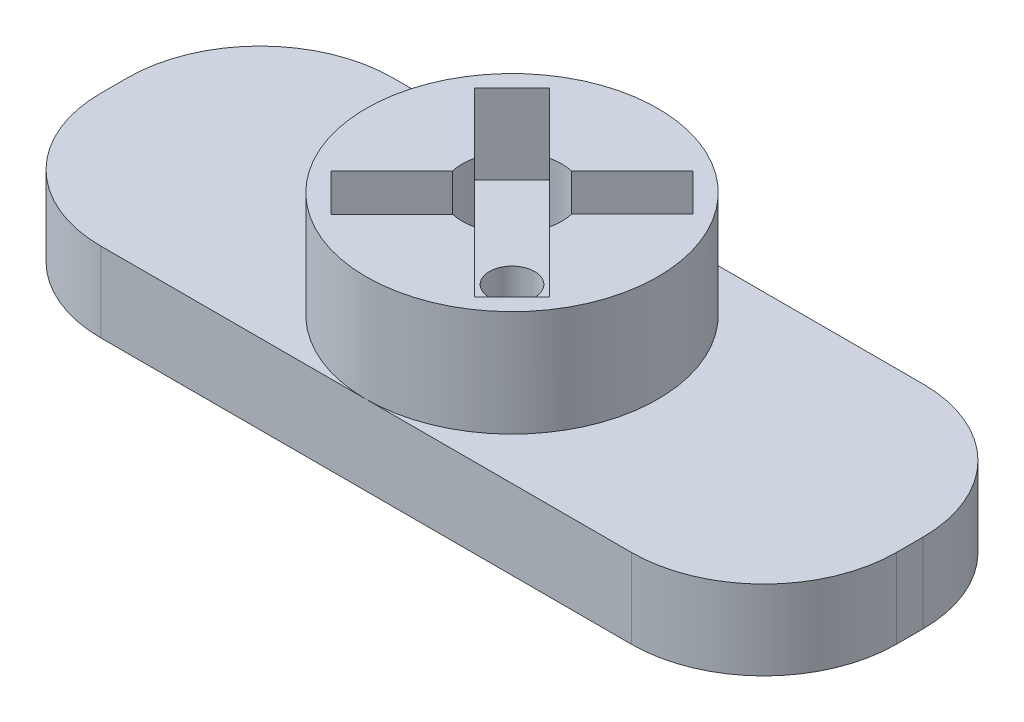
SolidWorks part; units mm, degrees
ref_plane "Płaszczyzna przednia" through (0, 0, 0) normal (0, 0, 1) x (1, 0, 0)
ref_plane "Płaszczyzna górna" through (0, 0, 0) normal (0, 1, 0) x (1, 0, 0)
ref_plane "Płaszczyzna prawa" through (0, 0, 0) normal (1, 0, 0) x (0, 0, -1)
sketch "Sketch1" plane through (0, 0, 0) normal (0, 1, 0) x (1, 0, 0)
  line L5 (-20.01, -11) -> (20.01, -11)
  line L6 (-30, -1.01) -> (-30, 1.01)
  line L7 (-20.01, 11) -> (20.01, 11)
  line L8 (30, -1.01) -> (30, 1.01)
  line L9 (-30, -11) -> (30, 11) construction
  line L10 (-30, 11) -> (30, -11) construction
  arc A0 (-20.01, -11) -> (-30, -1.01) centre (-20.01, -1.01) cw
  arc A1 (20.01, -11) -> (30, -1.01) centre (20.01, -1.01) ccw
  arc A2 (20.01, 11) -> (30, 1.01) centre (20.01, 1.01) cw
  arc A3 (-30, 1.01) -> (-20.01, 11) centre (-20.01, 1.01) cw
  point P0 (0, 0)
  point P1 (0, 0)
  dimension "D3" = 9.99
  dimension "D1" = 60
  dimension "D2" = 22
extrude "Boss-Extrude1" add sketch "Sketch1" along normal blind 6
sketch "Sketch2" plane through (0, 6, 0) normal (0, 1, 0) x (1, 0, 0)
  line L0 (0, 0) -> (-3, 0) construction
  line L1 (0, 0) -> (3, 0) construction
  circle A3 centre (0, 0) radius 11
extrude "Boss-Extrude2" add sketch "Sketch2" along normal blind 8
sketch "Sketch5" plane through (0, 14, 0) normal (0, 1, 0) x (1, 0, 0)
  line L0 (-6.8226, 6.8246) -> (-5.4081, 8.2386) construction
  line L39 (-5.4081, 8.2386) -> (-6.8226, 6.8246) construction
  line L40 (-6.8226, 6.8246) -> (-8.237, 5.4106) construction
  line L41 (6.8226, 6.8246) -> (5.4085, 8.239) construction
  line L42 (6.8226, 6.8246) -> (8.2366, 5.4102) construction
  line L43 (6.8226, -6.8246) -> (8.237, -5.4106) construction
  line L44 (6.8226, -6.8246) -> (5.4081, -8.2386) construction
  line L45 (-6.8226, -6.8246) -> (-8.2366, -5.4102) construction
  line L46 (-6.8226, -6.8246) -> (-5.4085, -8.239) construction
  line L47 (-8.237, 5.4106) -> (-3.6571, 0.8294)
  line L48 (5.4081, -8.2386) -> (8.237, -5.4106)
  line L49 (8.237, -5.4106) -> (3.6571, -0.8294)
  line L50 (-5.4081, 8.2386) -> (-8.237, 5.4106)
  line L51 (-5.4085, -8.239) -> (-0.8283, -3.6574)
  line L52 (8.2366, 5.4102) -> (5.4085, 8.239)
  line L53 (5.4085, 8.239) -> (0.8283, 3.6574)
  line L54 (-8.2366, -5.4102) -> (-5.4085, -8.239)
  line L55 (0.8283, -3.6574) -> (5.4081, -8.2386)
  line L56 (3.6571, 0.8294) -> (8.2366, 5.4102)
  line L58 (-0.8283, 3.6574) -> (-5.4081, 8.2386)
  line L60 (-3.6571, -0.8294) -> (-8.2366, -5.4102)
  arc A8 (-0.8283, -3.6574) -> (0.8283, -3.6574) centre (0, 0) ccw
  arc A10 (3.6571, -0.8294) -> (3.6571, 0.8294) centre (0, 0) ccw
  arc A11 (0.8283, 3.6574) -> (-0.8283, 3.6574) centre (0, 0) ccw
  arc A12 (-3.6571, 0.8294) -> (-3.6571, -0.8294) centre (0, 0) ccw
  dimension "D6" = 2
  dimension "D7" = 9.65
  dimension "D8" = 9.65
  dimension "D9" = 9.65
  dimension "D10" = 9.65
extrude "Cut-Extrude1" cut sketch "Sketch5" against normal blind 6
sketch "Sketch12" plane through (0, 0, 0) normal (0, -1, 0) x (1, 0, 0)
  circle A0 centre (0, 0) radius 6
extrude "Cut-Extrude2" cut sketch "Sketch12" against normal blind 4
sketch "Sketch18" plane through (0, 4, 0) normal (0, -1, 0) x (-1, 0, 0)
  point P0 (0, 0)
hole_wizard "CSK for M3 Countersunk Flat Head Screw3" positions "Sketch18" profile "Sketch17" countersink size "M3" standard "ISO" end condition through all
sketch "Sketch17" plane through (0, 4, 0) normal (1, 0, 0) x (0, 0, -1)
  line L0 (0, 0) -> (0, 10)
  line L1 (0, 10) -> (1.7, 10)
  line L2 (1.7, 10) -> (1.7, 1.45)
  line L3 (1.7, 1.45) -> (3.15, 0)
  line L5 (3.15, 0) -> (0, 0)
  line L6 (-1.7, 1.45) -> (-3.15, 0) construction
  line L11 (0, -6.35) -> (0, 107.95) construction
  dimension "Thru Hole Dia." = 3.4
  dimension "Thru Hole Depth" = 10
  dimension "Near C'Sink Dia." = 6.3
  dimension "Near C'Sink Angle" = 90
